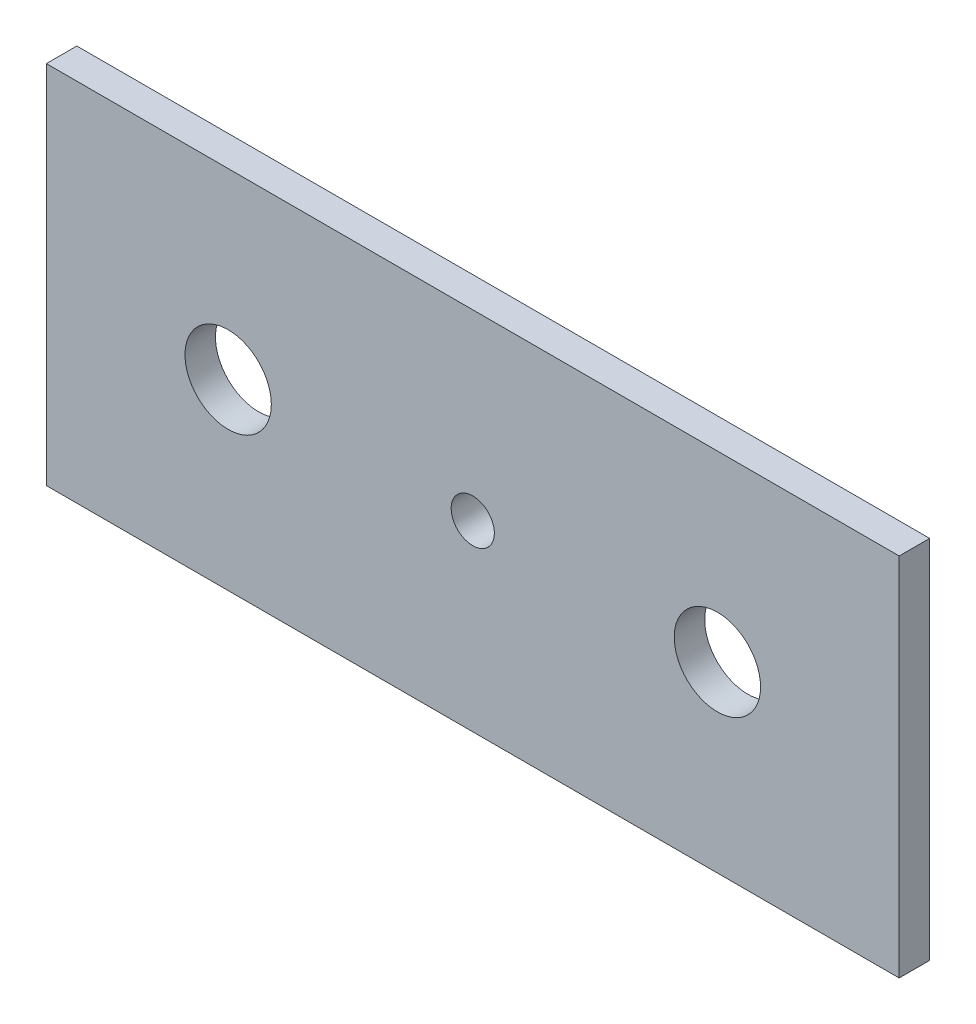
SolidWorks part; units mm, degrees
material "Plain Carbon Steel"
ref_plane "Front Plane" through (0, 0, 0) normal (0, 0, 1) x (1, 0, 0)
ref_plane "Top Plane" through (0, 0, 0) normal (0, 1, 0) x (1, 0, 0)
ref_plane "Right Plane" through (0, 0, 0) normal (1, 0, 0) x (0, 0, -1)
sketch "Sketch1" plane through (0, 0, 0) normal (0, 0, 1) x (1, 0, 0)
  line L1 (44.45, -19.05) -> (-44.45, -19.05)
  line L2 (44.45, -19.05) -> (44.45, 19.05)
  line L3 (44.45, 19.05) -> (-44.45, 19.05)
  line L4 (-44.45, -19.05) -> (-44.45, 19.05)
  point P0 (44.45, 0)
  point P7 (0, 19.05)
  point P8 (-44.45, 0)
  dimension "D2" = 38.1
  dimension "D3" = 88.9
extrude "Boss-Extrude1" add sketch "Sketch1" against normal blind 3.175
hole_wizard "M4 Clearance Hole1" positions "Sketch4" profile "Sketch3" hole size "M4" standard "ANSI Metric" end condition through all
sketch "Sketch4" plane through (0, 0, 0) normal (0, 0, 1) x (1, 0, 0)
  point P0 (0, 0)
sketch "Sketch3" plane through (0, 0, 0) normal (1, 0, 0) x (0, -1, 0)
  line L0 (0, 0) -> (0, 3.175)
  line L1 (0, 3.175) -> (2.25, 3.175)
  line L2 (2.25, 3.175) -> (2.25, 0)
  line L5 (2.25, 0) -> (0, 0)
  line L11 (0, -6.35) -> (0, 107.95) construction
  dimension "Thru Hole Dia." = 4.5
  dimension "Thru Hole Depth" = 3.175
hole_wizard "M8 Clearance Hole1" positions "Sketch7" profile "Sketch6" hole size "M8" standard "ANSI Metric" end condition through all
sketch "Sketch7" plane through (0, 0, 0) normal (0, 0, 1) x (1, 0, 0)
  circle A2 centre (-25.5, 0) radius 3.5 construction
  circle A3 centre (25.5, 0) radius 3.5 construction
  point P0 (-25.5, 0)
  point P3 (25.5, 0)
  point P18 (0, 0)
  point P25 (0, 0)
sketch "Sketch6" plane through (-25.5, 0, 0) normal (1, 0, 0) x (0, -1, 0)
  line L0 (0, 0) -> (0, 3.175)
  line L1 (0, 3.175) -> (4.5, 3.175)
  line L2 (4.5, 3.175) -> (4.5, 0)
  line L5 (4.5, 0) -> (0, 0)
  line L11 (0, -6.35) -> (0, 107.95) construction
  dimension "Thru Hole Dia." = 9
  dimension "Thru Hole Depth" = 3.175
